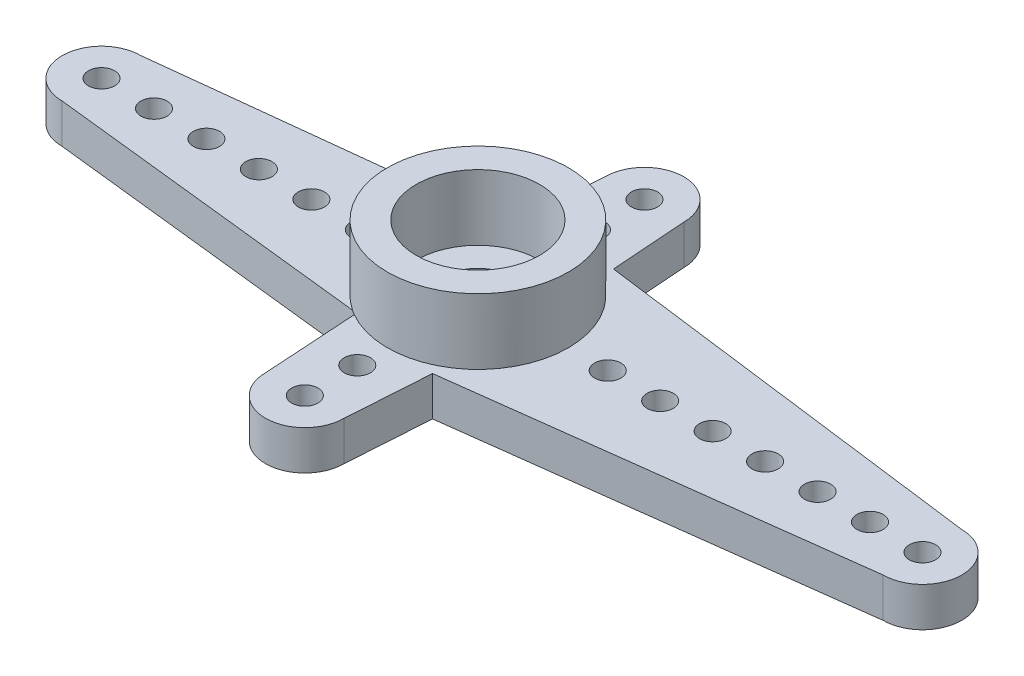
SolidWorks part; units mm, degrees
ref_plane "Front Plane" through (0, 0, 0) normal (0, 0, 1) x (1, 0, 0)
ref_plane "Top Plane" through (0, 0, 0) normal (0, 1, 0) x (1, 0, 0)
ref_plane "Right Plane" through (0, 0, 0) normal (1, 0, 0) x (0, 0, -1)
sketch "Sketch1" plane through (0, 0, 0) normal (0, 1, 0) x (1, 0, 0)
  line L0 (16.95, 0) -> (-14.35, 0) construction
  line L2 (16.95, 1.5) -> (1.7085, 3.4623)
  line L3 (1.7085, 3.4623) -> (1.7085, -3.4377) construction
  line L4 (1.7085, -3.4377) -> (16.95, -1.5)
  line L5 (-14.35, 1.5) -> (-1.7335, 2.9093)
  line L6 (-1.7335, 2.9093) -> (-1.7335, -2.8907) construction
  line L7 (-14.35, -1.5) -> (-1.7335, -2.8907)
  line L8 (0, 0) -> (0, 6.35) construction
  line L10 (1.5, 6.35) -> (1.7085, 3.4623)
  line L11 (-1.5, 6.35) -> (-1.7335, 2.9093)
  line L12 (0, 0) -> (0, -6.6) construction
  line L14 (-1.7335, -2.8907) -> (-1.5, -6.6)
  line L15 (1.5, -6.6) -> (1.7085, -3.4377)
  circle A0 centre (0, 0) radius 3.45 construction
  circle A1 centre (0, 0) radius 1.275
  circle A2 centre (0, 0) radius 2.35
  circle A3 centre (16.95, 0) radius 0.5
  circle A4 centre (12.95, 0) radius 0.5
  circle A5 centre (14.95, 0) radius 0.5
  circle A6 centre (10.95, 0) radius 0.5
  circle A7 centre (8.95, 0) radius 0.5
  circle A9 centre (6.95, 0) radius 0.5
  circle A10 centre (4.95, 0) radius 0.5
  circle A11 centre (-14.35, 0) radius 0.5
  circle A12 centre (-12.35, 0) radius 0.5
  circle A13 centre (-10.35, 0) radius 0.5
  circle A14 centre (-8.35, 0) radius 0.5
  circle A15 centre (-6.35, 0) radius 0.5
  circle A16 centre (-4.35, 0) radius 0.5
  arc A17 (-14.35, 1.5) -> (-14.35, -1.5) centre (-14.35, 0) ccw
  arc A18 (16.95, -1.5) -> (16.95, 1.5) centre (16.95, 0) ccw
  arc A19 (1.5, 6.35) -> (-1.5, 6.35) centre (0, 6.35) ccw
  circle A20 centre (0, 6.35) radius 0.5
  circle A21 centre (0, 4.35) radius 0.5
  arc A22 (-1.5, -6.6) -> (1.5, -6.6) centre (0, -6.6) ccw
  circle A23 centre (0, -6.6) radius 0.5
  circle A24 centre (0, -4.6) radius 0.5
  dimension "D1" = 16.95
  dimension "D2" = 2
  dimension "D3" = 2.55
  dimension "D4" = 4.7
  dimension "D5" = 6.9
  dimension "D6" = 1.5
  dimension "D7" = 14.35
  dimension "D8" = 6.6
  dimension "D9" = 6.35
sketch3d "3DSketch2" plane through (0, 0, 0) normal (0, 0, 1) x (1, 0, 0)
  dimension "D1" = 1.5
sketch "Sketch6" plane through (0, 1.5, 0) normal (0, 1, 0) x (1, 0, 0)
  circle A0 centre (0, 0) radius 1.275
  circle A1 centre (0, 0) radius 2.35
  circle A2 centre (0, 0) radius 3.45
extrude "Boss-Extrude1" add sketch "Sketch1" along normal blind 1.5 contours L14 A22 L15 L4 A18 L2 L10 A19 L11 L5 A17 L7 A24 A23 A2 A3 A4 A5 A6 A7 A9 A10 A11 A12 A13 A14 A15 A16 A20 A21 region at (18.0717, 0, 0)
extrude "Boss-Extrude2" add sketch "Sketch6" against normal blind 0.5 contours A1 A0 region at (-2.2835, 1.5, 0)
extrude "Boss-Extrude3" add sketch "Sketch6<3>" along normal blind 2.5 contours A2 A1 region at (-3.3524, 1.5, 0)
sketch "Sketch6<3>" plane through (0, 1.5, 0) normal (0, 1, 0) x (1, 0, 0) same geometry as "Sketch6"
